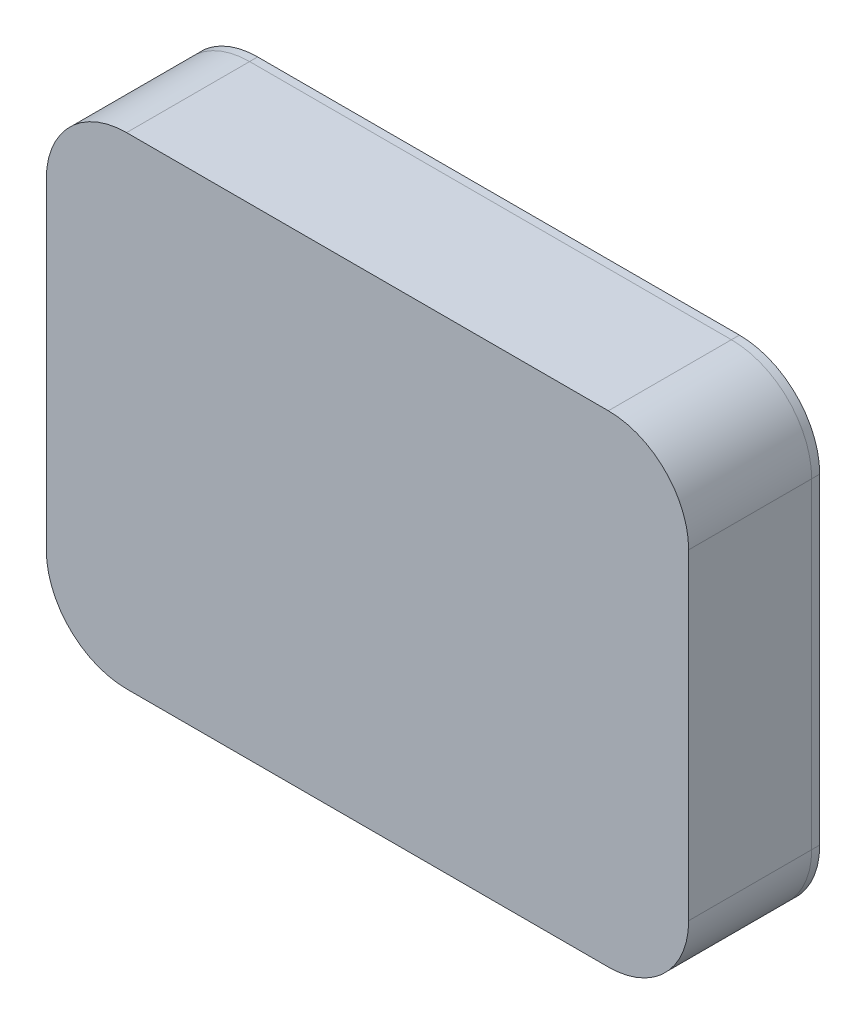
SolidWorks part; units mm, degrees
ref_plane "Plan de face" through (0, 0, 0) normal (0, 0, 1) x (1, 0, 0)
ref_plane "Plan de dessus" through (0, 0, 0) normal (0, 1, 0) x (1, 0, 0)
ref_plane "Plan de droite" through (0, 0, 0) normal (1, 0, 0) x (0, 0, -1)
sketch "Esquisse1" plane through (0, 0, 0) normal (0, 0, 1) x (1, 0, 0)
  line L1 (-30, 30) -> (30, 30)
  line L2 (-40, 20) -> (-40, -20)
  line L3 (-30, -30) -> (30, -30)
  line L4 (40, 20) -> (40, -20)
  line L5 (-40, 30) -> (40, -30) construction
  line L6 (-40, -30) -> (40, 30) construction
  arc A0 (-40, -20) -> (-30, -30) centre (-30, -20) ccw
  arc A1 (30, -30) -> (40, -20) centre (30, -20) ccw
  arc A2 (30, 30) -> (40, 20) centre (30, 20) cw
  arc A3 (-30, 30) -> (-40, 20) centre (-30, 20) ccw
  point P0 (0, 0)
  dimension "D1" = 10
  dimension "D2" = 40
  dimension "D3" = 60
sketch "profil" plane through (0, 0, 0) normal (1, 0, 0) x (0, 0, -1)
  line L0 (0, -28.4) -> (5.2972, -28.4)
  line L1 (5.2972, -28.4) -> (14.1228, -23.8)
  line L3 (14.1228, -30) -> (0, -30)
  line L4 (0, -30) -> (0, -28.4)
  line L6 (0, -20) -> (0, -30) construction
  line L7 (0, -30) -> (0, 30) construction
  line L8 (14.1228, -23.8) -> (14.1228, -25.4) construction
  line L9 (14.1228, -28.4) -> (14.1228, -30) construction
  line L10 (14.1228, -23.8) -> (15.1228, -23.8)
  line L11 (15.1228, -23.8) -> (15.1228, -25.4)
  line L12 (15.1228, -25.4) -> (14.1228, -25.4)
  line L13 (14.1228, -30) -> (15.1228, -30)
  line L14 (15.1228, -30) -> (15.1228, -28.4)
  line L15 (15.1228, -28.4) -> (14.1228, -28.4)
  arc A0 (14.1228, -25.4) -> (14.1228, -28.4) centre (14.1228, -26.9) ccw
  dimension "D1" = 3
  dimension "D3" = 14.1228
  dimension "D4" = 1
sweep "Balayage1" add profiles "profil" path "Esquisse1"
extrude "Boss.-Extru.1" add sketch "Esquisse1<3>" along normal blind 1.2
sketch "Esquisse1<3>" plane through (0, 0, 0) normal (0, 0, 1) x (1, 0, 0) same geometry as "Esquisse1"
fillet "Congé1" radius 2 9 edges at (-35.9397, 25.9397, 0) (-38.4, 0, 0) (-35.9397, -25.9397, 0) (-15, -28.4, 0) (15, -28.4, 0) (35.9397, -25.9397, 0) (38.4, 0, 0) (35.9397, 25.9397, 0) (0, 28.4, 0)
sketch "Esquisse2" plane through (0, 0, 0) normal (0, 0, -1) x (-1, 0, 0)
  circle A0 centre (-27.6661, 18.8186) radius 2.5
  circle A1 centre (-27.6661, -16.9814) radius 2.5
  circle A2 centre (19.6339, -17.0814) radius 2.5
  circle A3 centre (20.1225, 18.0592) radius 2.5
  dimension "D1" = 5
  dimension "D2" = 5
  dimension "D3" = 5
  dimension "D4" = 5
extrude "Plot" add sketch "Esquisse2" along normal blind 3
fillet "Congé2" radius 5 4 edges at (-17.1339, -17.0814, 0) (30.1661, -16.9814, 0) (-17.6225, 18.0592, 0) (30.1661, 18.8186, 0)
equation "\"buse\"=0.4"
equation "\"coque\"= \"buse\" * 4"
equation "\"diam_silicone\"=3"
equation "\"D1@profil\" = \"diam_silicone\""
equation "\"couche\"=0.2"
equation "\"D1@Boss.-Extru.1\"=\"fond\""
equation "\"fond\"= \"couche\" * 6"
equation "\"dim_ext\"= 40"
equation "\"D2@Esquisse1\"=\"dim_ext\""
equation "\"dim_ext_L\"=60"
equation "\"D3@Esquisse1\"=\"dim_ext_L\""
equation "\"hauteur_boitier\"=14.1228"
equation "\"D3@profil\"=\"hauteur_boitier\""
